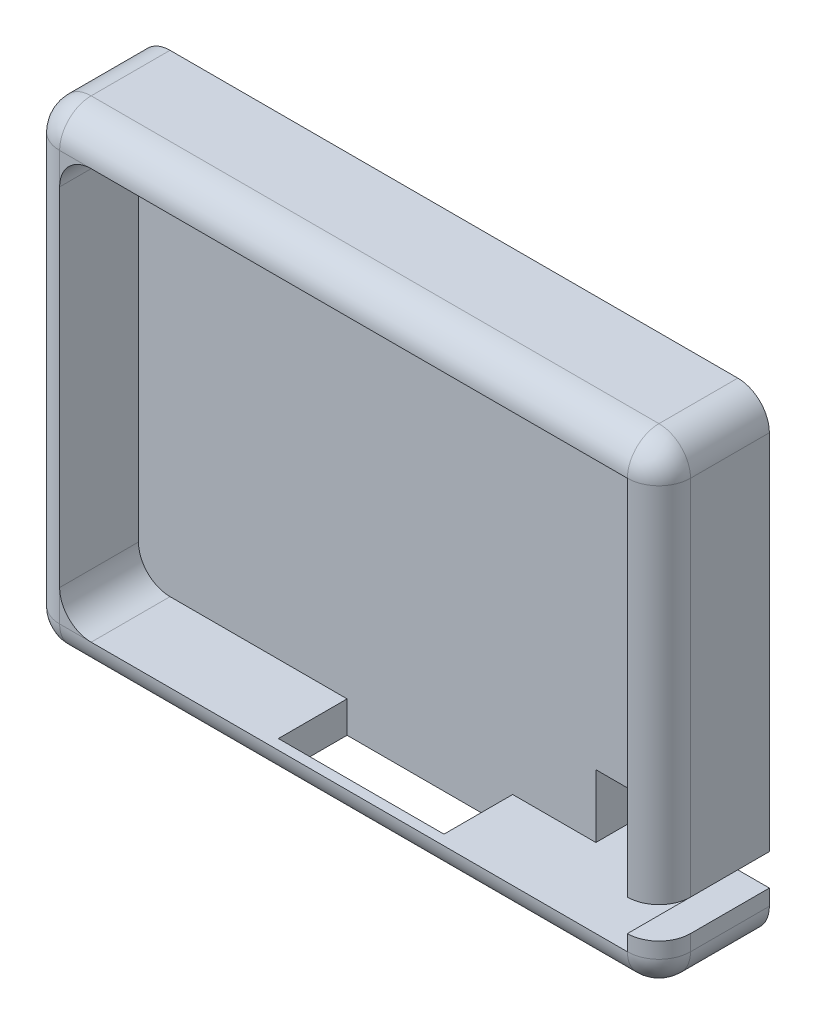
SolidWorks part; units mm, degrees
ref_plane "前视基准面" through (0, 0, 0) normal (0, 0, 1) x (1, 0, 0)
ref_plane "上视基准面" through (0, 0, 0) normal (0, 1, 0) x (1, 0, 0)
ref_plane "右视基准面" through (0, 0, 0) normal (1, 0, 0) x (0, 0, -1)
sketch "Sketch1" plane through (0, 0, 0) normal (0, 0, 1) x (1, 0, 0)
  line L0 (20, 30) -> (20, 0) construction
  line L1 (0, 0) -> (40, 0)
  line L2 (0, 0) -> (0, 30)
  line L3 (0, 30) -> (40, 30)
  line L4 (40, 0) -> (40, 30)
  line L5 (0, 15) -> (40, 15) construction
  point P9 (20, 15)
  dimension "D1" = 40
  dimension "D2" = 30
extrude "Boss-Extrude1" add sketch "Sketch1" along normal blind 7
sketch "Sketch2" plane through (0, 0, 7) normal (0, 0, 1) x (1, 0, 0)
  line L0 (0, 30) -> (40, 0) construction
  line L1 (0, 0) -> (40, 0) construction
  line L2 (40, 0) -> (40, 30) construction
  line L3 (40, 30) -> (0, 0) construction
  line L5 (2, 28) -> (38, 28)
  line L6 (2, 28) -> (2, 2)
  line L7 (2, 2) -> (38, 2)
  line L8 (38, 28) -> (38, 2)
  line L9 (2, 28) -> (38, 2) construction
  line L10 (2, 2) -> (38, 28) construction
  point P11 (20, 15)
  dimension "D1" = 36
  dimension "D2" = 26
extrude "Cut-Extrude1" cut sketch "Sketch2" against normal blind 5
fillet "Fillet1" radius 2 2 edges at (2, 28, 4.5) (2, 2, 4.5)
fillet "Fillet2" radius 2 8 edges at (20, 0, 7) (40, 15, 7) (20, 30, 7) (0, 15, 7) (0, 0, 3.5) (40, 0, 3.5) (40, 30, 3.5) (0, 30, 3.5)
sketch "Sketch3" plane through (0, 0, 2) normal (0, 0, 1) x (1, 0, 0)
  line L1 (38, 2) -> (31, 2)
  line L2 (38, 2) -> (38, 6)
  line L3 (38, 6) -> (31, 6)
  line L4 (31, 2) -> (31, 6)
  dimension "D1" = 7
  dimension "D2" = 4
extrude "Cut-Extrude2" cut sketch "Sketch3" against normal up to surface (2 mm away) up to face at (20, 15, 0)
sketch "Sketch6" plane through (0, 2, 0) normal (0, 1, 0) x (1, 0, 0)
  line L0 (31, -2) -> (38, -2) construction
  line L1 (38, 0) -> (38, -7) construction
  line L2 (38, -2) -> (38, -4.7524) construction
  line L3 (38, -4.7524) -> (20.4758, -4.7524) construction
  line L4 (4, -2) -> (31, -2) construction
  line L6 (15.2258, -2) -> (25.7258, -2)
  line L7 (15.2258, -2) -> (15.2258, -6.356)
  line L8 (15.2258, -6.356) -> (25.7258, -6.356)
  line L9 (25.7258, -2) -> (25.7258, -6.356)
  dimension "D2" = 10.5
extrude "Cut-Extrude3" cut sketch "Sketch6" against normal up to surface (2 mm away) up to face at (20, 0, 2.5)
sketch "Sketch7" plane through (0, 0, 0) normal (0, 0, -1) x (-1, 0, 0)
  line L0 (-38, 4) -> (-40, 4) construction
  line L1 (-38, 2) -> (-38, 6) construction
  line L2 (-40, 2) -> (-40, 28) construction
  line L3 (-38, 6) -> (-40, 4) construction
  line L4 (-40, 4) -> (-38, 2) construction
  line L5 (-39, 4) -> (-39, 5) construction
  line L6 (-39, 5) -> (-39, 3) construction
  line L7 (-39, 5) -> (-38, 5) construction
  line L8 (-39, 5) -> (-40, 5) construction
  line L9 (-39, 3) -> (-38, 3) construction
  line L10 (-39, 3) -> (-40, 3) construction
  line L11 (-38, 5) -> (-40, 5)
  line L12 (-38, 3) -> (-40, 3)
  line L13 (-40, 5) -> (-40, 3)
  line L14 (-38, 5) -> (-38, 3)
extrude "Cut-Extrude4" cut sketch "Sketch7" against normal blind 10
